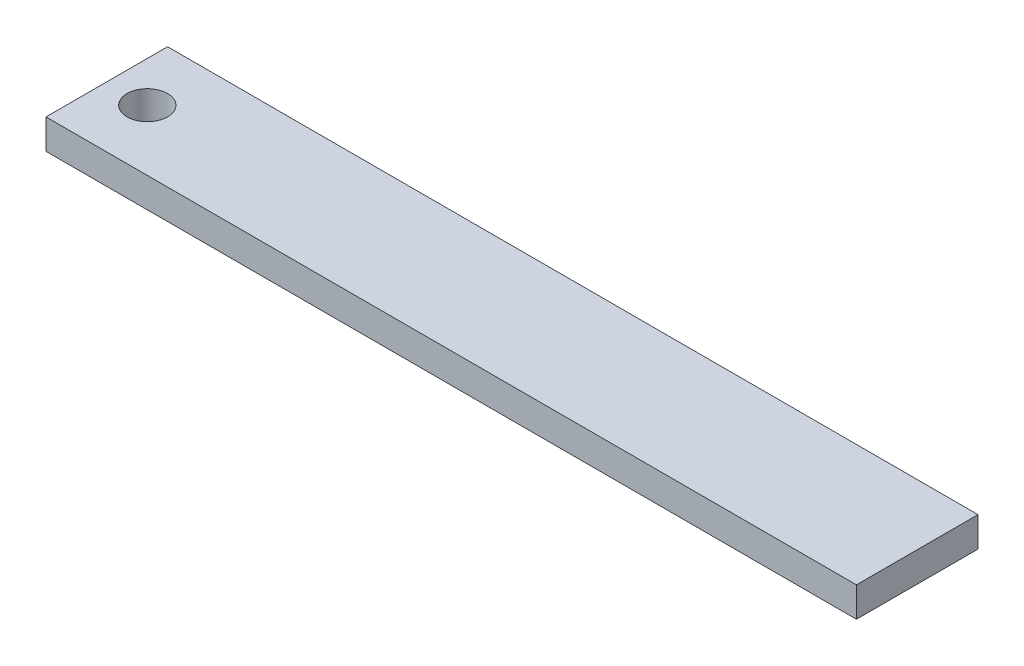
SolidWorks part; units mm, degrees
ref_plane "Front Plane" through (0, 0, 0) normal (0, 0, 1) x (1, 0, 0)
ref_plane "Top Plane" through (0, 0, 0) normal (0, 1, 0) x (1, 0, 0)
ref_plane "Right Plane" through (0, 0, 0) normal (1, 0, 0) x (0, 0, -1)
sketch "Sketch1" plane through (0, 0, 0) normal (0, 1, 0) x (1, 0, 0)
  line L0 (-10, 0) -> (-2.4054, 0) construction
  line L1 (-10, 1.5) -> (10, 1.5)
  line L2 (-10, 1.5) -> (-10, -1.5)
  line L3 (-10, -1.5) -> (10, -1.5)
  line L4 (10, 1.5) -> (10, -1.5)
  line L5 (-10, 1.5) -> (10, -1.5) construction
  line L6 (-10, -1.5) -> (10, 1.5) construction
  circle A0 centre (-9, 0) radius 0.5
  point P0 (0, 0)
  dimension "D3" = 1
  dimension "D1" = 3
  dimension "D2" = 20
base flange "Base-Flange1" sketch "Sketch1" thickness 0.7366 reverse thickness direction no parameters "D1"=0.7366
sketch "Bend-Lines1" plane through (0, 0, 0) normal (0, 1, 0) x (1, 0, 0)
sketch "Bounding-Box1" plane through (0, 0, 0) normal (0, 1, 0) x (1, 0, 0)
sheet metal parameters "Sheet-Metal(1)" thickness 0.7366 parameters "D1"=0.7366
flat pattern "Flat-Pattern(1)" [suppressed]
sketch "Bend-Lines2" plane through (0, 0, 0) normal (0, 1, 0) x (1, 0, 0)
sketch "Bounding-Box2" [suppressed] plane through (0, 0, 0) normal (0, 1, 0) x (1, 0, 0)
